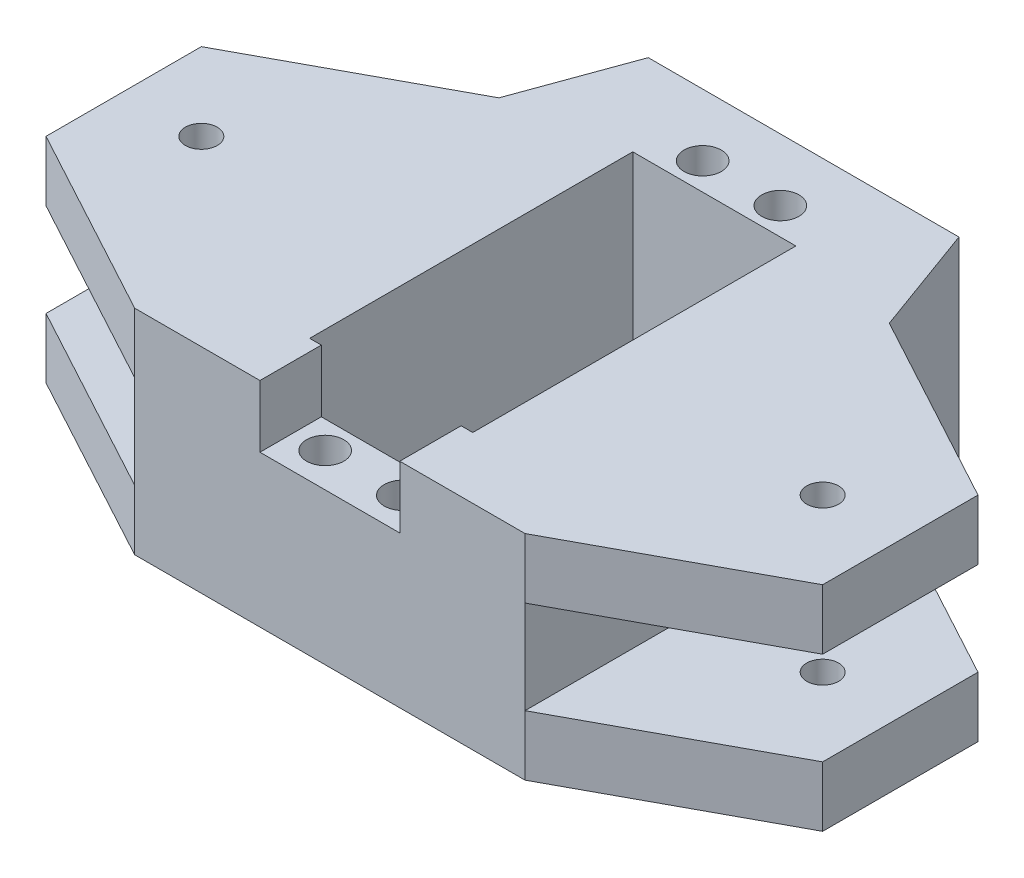
SolidWorks part; units mm, degrees
ref_plane "Front Plane" through (0, 0, 0) normal (0, 0, 1) x (1, 0, 0)
ref_plane "Top Plane" through (0, 0, 0) normal (0, 1, 0) x (1, 0, 0)
ref_plane "Right Plane" through (0, 0, 0) normal (1, 0, 0) x (0, 0, -1)
sketch "Sketch1" plane through (0, 0, 0) normal (0, 1, 0) x (1, 0, 0)
  line L0 (0, 0) -> (0, 55585.7092) construction
  line L1 (0, 0) -> (55585.7092, 0) construction
  line L2 (20, 37.5477) -> (-20, 37.5477)
  line L3 (-20, 37.5477) -> (-25.1303, 23.4523)
  line L4 (-25.1303, 23.4523) -> (-50, 10)
  line L5 (-50, 10) -> (-50, -10)
  line L11 (50, 10) -> (50, -10)
  line L12 (25.1303, 23.4523) -> (50, 10)
  line L13 (20, 37.5477) -> (25.1303, 23.4523)
  line L14 (25.1303, -23.4523) -> (50, -10)
  line L15 (-25.1303, -23.4523) -> (-50, -10)
  line L19 (25.1303, -23.4523) -> (-25.1303, -23.4523)
  point P7 (50, 0)
  point P12 (-50, 0)
  point P14 (0, -10.7407)
  point P19 (0, 37.5477)
  dimension "D1" = 40
  dimension "D2" = 20
  dimension "D3" = 61
  dimension "D4" = 100
  dimension "D5" = 110
  dimension "D8" = 15
extrude "Main-Body" add sketch "Sketch1" along normal mid plane 27.5
sketch "Sketch2" plane through (0, 13.75, 0) normal (0, 1, 0) x (1, 0, 0)
  line L0 (0, 47.5477) -> (0, -49952.4523) construction
  line L2 (20, 37.5477) -> (-20, 37.5477) construction
  line L3 (-6.4366, -21.4523) -> (49993.5634, -21.4523) construction
  line L4 (10.5, -15.5523) -> (-10.5, -15.5523)
  line L5 (-10.5, -15.5523) -> (-10.5, 26.0477)
  line L6 (-10.5, 26.0477) -> (10.5, 26.0477)
  line L7 (10.5, -15.5523) -> (10.5, 26.0477)
  line L8 (0, -23.4523) -> (50000, -23.4523) construction
  line L10 (-5, 29.5477) -> (5, 29.5477) construction
  line L11 (-5, -19.0523) -> (5, -19.0523) construction
  line L12 (-25.1303, -23.4523) -> (25.1303, -23.4523) construction
  circle A0 centre (-5, -19.0523) radius 2.4
  circle A1 centre (5, -19.0523) radius 2.4
  circle A2 centre (-5, 29.5477) radius 2.4
  circle A3 centre (5, 29.5477) radius 2.4
  point P22 (0, -15.5523)
  point P23 (0, 26.0477)
  point P28 (0, 37.5477)
  point P29 (0, -19.0523)
  point P30 (0, 29.5477)
  point P31 (0, 0)
  point P32 (10.8957, 7.0477)
  dimension "D1" = 4.8
  dimension "D4" = 4.8
  dimension "D10" = 4.8
  dimension "D11" = 4.8
  dimension "D3" = 10
  dimension "D5" = 48.6
  dimension "D6" = 10
  dimension "D7" = 21
  dimension "D8" = 3.5
  dimension "D9" = 3.5
  dimension "D2" = 2
extrude "Servo-Cutout" cut sketch "Sketch2" against normal blind 30
sketch "Sketch3" plane through (0, 0, 23.4523) normal (0, 0, 1) x (1, 0, 0)
  line L0 (0, 0) -> (0, 50000) construction
  line L1 (0, 0) -> (48695.3801, 0) construction
  line L3 (9, 13.75) -> (-9, 13.75)
  line L4 (-9, 13.75) -> (-9, 5.75)
  line L5 (-9, 5.75) -> (9, 5.75)
  line L6 (9, 13.75) -> (9, 5.75)
  line L7 (-25.1303, 13.75) -> (25.1303, 13.75) construction
  point P10 (0, 0)
  point P11 (0, 13.75)
  dimension "D1" = 18
  dimension "D2" = 8
  dimension "D3" = 0
extrude "Servo-Cable-Cutout" cut sketch "Sketch3" against normal up to surface (7.9 mm away) up to face at (0, 0, 15.5523)
sketch "Sketch4" plane through (0, 0, 23.4523) normal (0, 0, 1) x (1, 0, 0)
  line L0 (0, 0) -> (0, 50000) construction
  line L1 (50, 0) -> (50050, 0) construction
  line L2 (50, 13.75) -> (50, -13.75) construction
  line L3 (-50, -6) -> (-50, 6)
  line L4 (-50, 13.75) -> (-50, -13.75) construction
  line L5 (-50, 6) -> (-25.1303, 6)
  line L6 (-25.1303, 6) -> (-25.1303, -6)
  line L7 (-50, -6) -> (-25.1303, -6)
  line L10 (-25.1303, 13.75) -> (-25.1303, -13.75) construction
  point P7 (50, 0)
  point P15 (-25.1303, 0)
  point P16 (-50, 0)
  dimension "D1" = 0
  dimension "D2" = 12
extrude "Control-Arm-Cutout" cut sketch "Sketch4" against normal through all both and the other way through all
mirror "Mirror1" about plane through (0, 0, 0) normal (1, 0, 0) of "Control-Arm-Cutout"
sketch "Sketch5" plane through (0, 13.75, 0) normal (0, 1, 0) x (1, 0, 0)
  line L0 (-50, 0) -> (49950, 0) construction
  line L1 (-50, 10) -> (-50, -10) construction
  line L2 (0, 0) -> (0, 50000) construction
  circle A0 centre (-40, 0) radius 2.05
  point P4 (-50, 0)
  dimension "D1" = 4.1
  dimension "D2" = 10
extrude "Cut-Extrude4" cut sketch "Sketch5" against normal through all both and the other way through all
mirror "Mirror2" about plane through (0, 0, 0) normal (1, 0, 0) of "Cut-Extrude4"
equation "\"D10@Sketch2\"=\"D1@Sketch2\""
equation "\"D11@Sketch2\"=\"D1@Sketch2\""
